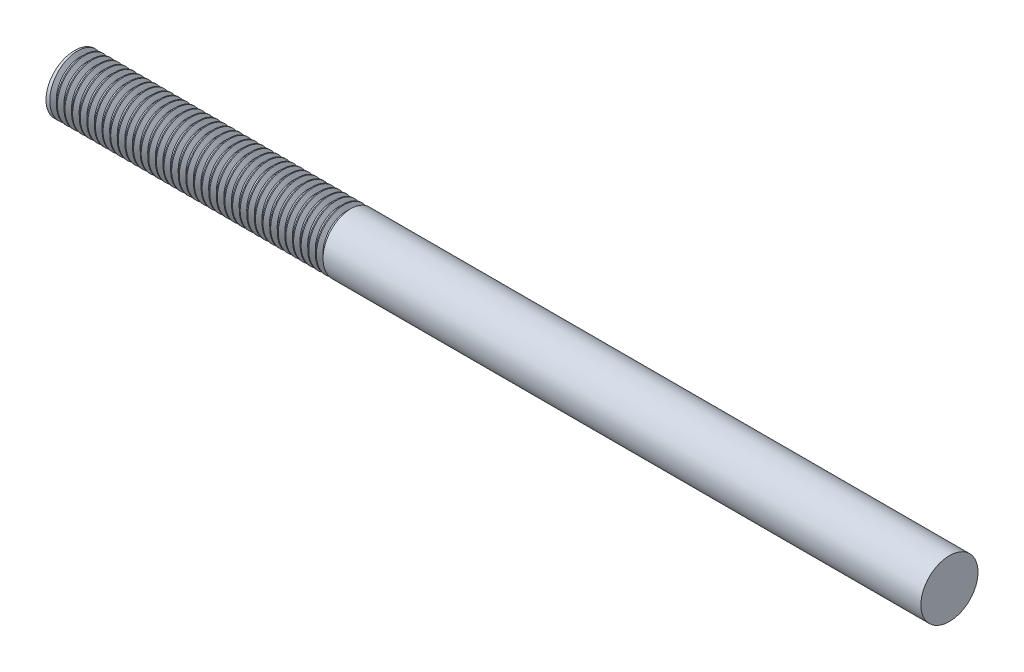
SolidWorks part; units mm, degrees
ref_plane "Front Plane" through (0, 0, 0) normal (0, 0, 1) x (1, 0, 0)
ref_plane "Top Plane" through (0, 0, 0) normal (0, 1, 0) x (1, 0, 0)
ref_plane "Right Plane" through (0, 0, 0) normal (1, 0, 0) x (0, 0, -1)
sketch "Sketch1" plane through (0, 0, 0) normal (0, 0, 1) x (1, 0, 0)
  line L2 (76.066, 26.3184) -> (76.066, 22.6354)
  line L7 (76.066, 22.6354) -> (-45.488, 22.6354)
  line L8 (-45.488, 22.6354) -> (-45.488, 26.6042)
  line L9 (-45.488, 26.6042) -> (76.066, 26.6042)
  line L10 (76.066, 26.3184) -> (76.066, 26.6042)
  line L11 (76.066, 26.6042) -> (76.066, 26.3184)
  dimension "D1" = 121.554
  dimension "D3" = 3.9688
revolve "Revolve1" add sketch "Sketch1" angle 360 about L7
thread "Thread1" pitch 1.0583 profile "Thread Profile1" start angle 0, offset 0, length 38.1, pitch 1.0583, diameter 7.9375
ref_plane "Plane1" through (-45.488, 22.6354, -3.9687) normal (0, -1, 0) x (0, 0, -1)
sketch "Thread Profile1" plane through (-45.488, 22.6354, -3.9687) normal (0, -1, 0) x (0, 0, -1)
  line L0 (0, 0) -> (0, 1.0583) construction
  line L11 (0, 0) -> (0, 0.926)
  line L12 (0, 0.926) -> (-0.5728, 0.5953)
  line L13 (-0.5728, 0.5953) -> (-0.5728, 0.3307)
  line L15 (-0.5728, 0.3307) -> (0, 0)
  line L17 (-0.5728, 0.463) -> (0, 0.463) construction
  point P2 (0, 0)
  dimension "Pitch" = 1.0583
  dimension "Profile_Angle" = 60
  dimension "Profile_Land" = 0.2646
  dimension "Profile_Height" = 0.5728
sketch3d "3DSketch1"
  circle A0 centre (76.066, 22.6354, 0) radius 3.9687 construction
  point P2 (80.0347, 22.6354, 0)
  point P6 (76.066, 22.6354, 0)
